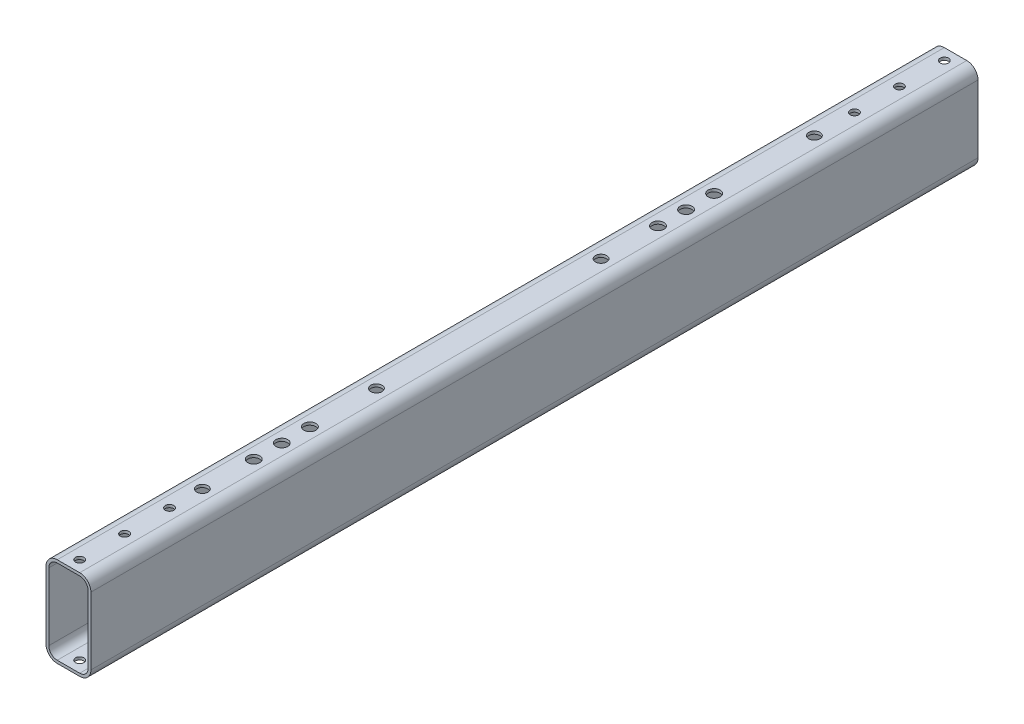
SolidWorks part; units mm, degrees
material "6061-T6 (SS)"
ref_plane "Front Plane" through (0, 0, 0) normal (0, 0, 1) x (1, 0, 0)
ref_plane "Top Plane" through (0, 0, 0) normal (0, 1, 0) x (1, 0, 0)
ref_plane "Right Plane" through (0, 0, 0) normal (1, 0, 0) x (0, 0, -1)
sketch "Sketch1" plane through (0, 0, 0) normal (0, 0, 1) x (1, 0, 0)
  line L1 (-6.35, -25.4) -> (6.35, -25.4)
  line L2 (-12.7, -19.05) -> (-12.7, 19.05)
  line L3 (-6.35, 25.4) -> (6.35, 25.4)
  line L4 (12.7, -19.05) -> (12.7, 19.05)
  line L5 (-12.7, -25.4) -> (12.7, 25.4) construction
  line L6 (-12.7, 25.4) -> (12.7, -25.4) construction
  arc A0 (-12.7, -19.05) -> (-6.35, -25.4) centre (-6.35, -19.05) ccw
  arc A1 (6.35, -25.4) -> (12.7, -19.05) centre (6.35, -19.05) ccw
  arc A2 (6.35, 25.4) -> (12.7, 19.05) centre (6.35, 19.05) cw
  arc A3 (-12.7, 19.05) -> (-6.35, 25.4) centre (-6.35, 19.05) cw
  point P0 (0, 0)
  dimension "D3" = 6.35
  dimension "D1" = 50.8
  dimension "D2" = 25.4
extrude "Extrude-Thin1" add sketch "Sketch1" along normal blind 501.65 thin thin type one direction reverse wall 1.5875
hole_wizard "3/16 (0.1875) Diameter Hole1" positions "3DSketch1" profile "Sketch3" hole size "3/16" standard "ANSI Inch" end condition through all
sketch3d "3DSketch1"
  line L1 (6.35, 25.4, 0) -> (-6.35, 25.4, 0) construction
  line L6 (0, 25.4, 501.65) -> (0, 25.4, 0) construction
  line L7 (6.35, 25.4, 501.65) -> (-6.35, 25.4, 501.65) construction
  point P57 (0, 25.4, 6.35)
  point P59 (0, 25.4, 31.75)
  point P61 (0, 25.4, 57.15)
  point P63 (0, 25.4, 469.9)
  point P65 (0, 25.4, 444.5)
  point P67 (0, 25.4, 495.3)
  dimension "D1" = 25.4
  dimension "D2" = 25.4
  dimension "D3" = 6.35
  dimension "D4" = 25.4
  dimension "D5" = 25.4
  dimension "D6" = 6.35
sketch "Sketch3" plane through (0, 25.4, 495.3) normal (1, 0, 0) x (0, 0, 1)
  line L0 (0, 0) -> (0, 50.8)
  line L1 (0, 50.8) -> (2.3812, 50.8)
  line L2 (2.3812, 50.8) -> (2.3812, 0)
  line L5 (2.3812, 0) -> (0, 0)
  line L11 (0, -6.35) -> (0, 107.95) construction
  dimension "Thru Hole Dia." = 4.7625
  dimension "Thru Hole Depth" = 50.8
hole_wizard "3/16 (0.195) Diameter Hole1" positions "Sketch4" profile "Sketch5" hole size "3/16" standard "ANSI Inch" end condition up to next
sketch "Sketch4" plane through (0, -25.4, 0) normal (0, -1, 0) x (-1, 0, 0)
  point P28 (3.175, -85.7193)
  point P31 (-3.175, -111.1193)
  point P34 (3.175, -136.5193)
  point P37 (-3.175, -161.9193)
  point P40 (3.175, -187.3193)
  point P43 (3.175, -339.7193)
  point P46 (-3.175, -365.1193)
  point P49 (3.175, -390.5193)
  point P52 (-3.175, -415.9193)
  point P60 (-3.175, -212.7193)
  point P63 (3.175, -238.1193)
  point P66 (-3.175, -263.5193)
  point P69 (3.175, -288.9193)
  point P72 (-3.175, -314.3193)
sketch "Sketch5" plane through (-3.175, -25.4, 85.7193) normal (1, 0, 0) x (0, 0, -1)
  line L0 (0, 0) -> (0, 1.5875)
  line L1 (0, 1.5875) -> (2.4765, 1.5875)
  line L2 (2.4765, 1.5875) -> (2.4765, 0)
  line L5 (2.4765, 0) -> (0, 0)
  line L11 (0, -6.35) -> (0, 107.95) construction
  dimension "Thru Hole Dia." = 4.953
  dimension "Thru Hole Depth" = 1.5875
hole_wizard "1/4 (0.25) Diameter Hole1" positions "Sketch7" profile "Sketch6" hole size "1/4" standard "ANSI Inch"
sketch "Sketch7" plane through (0, 25.4, 0) normal (0, 1, 0) x (1, 0, 0)
  point P6 (0, -79.831)
  point P9 (0, -425.9339)
  point P23 (0, -327.499)
  point P26 (0, -200.481)
sketch "Sketch6" plane through (0, 25.4, 79.831) normal (1, 0, 0) x (0, 0, 1)
  line L0 (0, 0) -> (0, 27.3077)
  line L1 (0, 27.3077) -> (3.175, 25.4)
  line L2 (3.175, 25.4) -> (3.175, 0)
  line L5 (3.175, 0) -> (0, 0)
  line L10 (0, 27.3077) -> (-3.175, 25.4) construction
  line L11 (0, -6.35) -> (0, 107.95) construction
  dimension "Hole Dia." = 6.35
  dimension "Hole Depth" = 25.4
  dimension "Drill Angle" = 118
hole_wizard "1/4 Clearance Hole1" positions "Sketch8" profile "Sketch9" hole size "1/4" standard "ANSI Inch"
sketch "Sketch8" plane through (381, 25.4, 250.825) normal (0, 1, 0) x (1, 0, 0)
  point P0 (381, 82.55)
  point P3 (381, 98.425)
  point P6 (381, 114.3)
  point P9 (381, -146.05)
  point P12 (381, -130.175)
  point P15 (381, -114.3)
  point P18 (-381, -146.05)
  point P21 (-381, -130.175)
  point P24 (-381, -114.3)
  point P27 (-381, 82.55)
  point P30 (-381, 98.425)
  point P33 (-381, 114.3)
sketch "Sketch9" plane through (762, 25.4, 168.275) normal (1, 0, 0) x (0, 0, 1)
  line L0 (0, 0) -> (0, 8.3798)
  line L1 (0, 8.3798) -> (3.3782, 6.35)
  line L2 (3.3782, 6.35) -> (3.3782, 0)
  line L3 (3.3782, 0) -> (0, 0)
  line L4 (0, 8.3798) -> (-3.3782, 6.35) construction
  line L5 (0, -6.35) -> (0, 107.95) construction
  dimension "Hole Dia." = 6.7564
  dimension "Hole Depth" = 6.35
  dimension "Drill Angle" = 118
